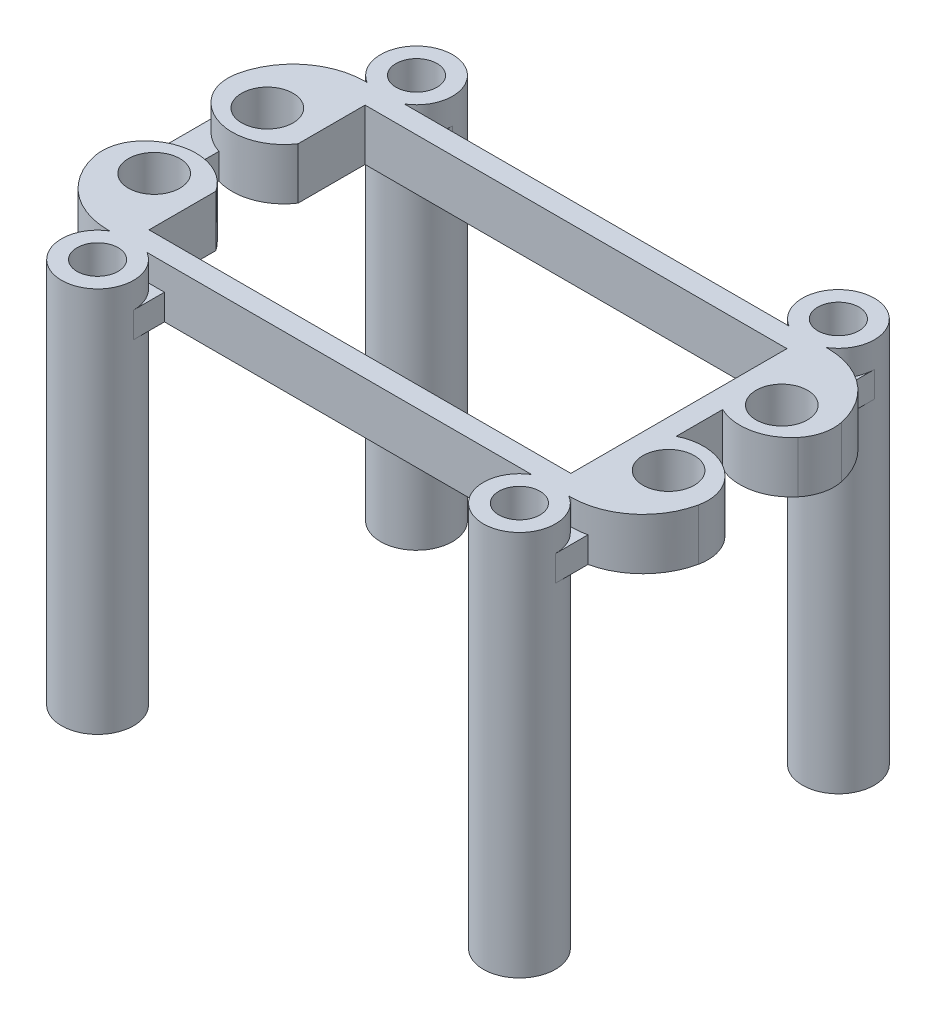
SolidWorks part; units mm, degrees
ref_plane "Front Plane" through (0, 0, 0) normal (0, 0, 1) x (1, 0, 0)
ref_plane "Top Plane" through (0, 0, 0) normal (0, 1, 0) x (1, 0, 0)
ref_plane "Right Plane" through (0, 0, 0) normal (1, 0, 0) x (0, 0, -1)
sketch "Sketch1" plane through (0, 0, 0) normal (0, 1, 0) x (1, 0, 0)
  line L0 (-20, 0) -> (-22, 0) construction
  line L1 (20.5, 10.5) -> (-20.5, 10.5)
  line L2 (20.5, 10.5) -> (20.5, -10.5)
  line L3 (20.5, -10.5) -> (-20.5, -10.5)
  line L4 (-20.5, 10.5) -> (-20.5, 4)
  line L5 (20.5, 10.5) -> (-20.5, -10.5) construction
  line L6 (20.5, -10.5) -> (-20.5, 10.5) construction
  line L7 (22.5, 12.5) -> (-22.5, 12.5)
  line L8 (22.5, 2.2557) -> (22.5, -2.2557)
  line L9 (22.5, -12.5) -> (-22.5, -12.5)
  line L11 (22.5, 12.5) -> (-22.5, -12.5) construction
  line L12 (22.5, -12.5) -> (-22.5, 12.5) construction
  line L16 (-20.5, -4) -> (-20.5, -10.5)
  line L17 (0, 0) -> (-37.8746, 0) construction
  line L18 (0, 0) -> (0, 8.5057) construction
  circle A0 centre (-25, 5.5) radius 2.5
  circle A1 centre (-25, -5.5) radius 2.5
  arc A4 (-22.5, 12.5) -> (-29.3504, 6.9605) centre (-22.5, 5.4945) ccw
  arc A5 (-20.5, 4) -> (-28.5206, 3.5732) centre (-24.6686, 6.761) cw
  arc A6 (-20.5, -4) -> (-28.5206, -3.5732) centre (-24.6686, -6.761) ccw
  arc A7 (-22.5, -12.5) -> (-29.3504, -6.9605) centre (-22.5, -5.4945) cw
  arc A8 (22.5, -12.5) -> (29.3504, -6.9605) centre (22.5, -5.4945) ccw
  circle A9 centre (25, -5.5) radius 2.5
  arc A10 (22.5, -2.2557) -> (28.5206, -3.5732) centre (24.6686, -6.761) cw
  circle A11 centre (25, 5.5) radius 2.5
  arc A12 (22.5, 2.2557) -> (28.5206, 3.5732) centre (24.6686, 6.761) ccw
  arc A13 (22.5, 12.5) -> (29.3504, 6.9605) centre (22.5, 5.4945) cw
  arc A14 (29.3504, -6.9605) -> (28.5206, -3.5732) centre (25.439, -6.1234) ccw
  arc A15 (28.5206, 3.5732) -> (29.3504, 6.9605) centre (25.439, 6.1234) ccw
  arc A16 (-28.5206, -3.5732) -> (-29.3504, -6.9605) centre (-25.439, -6.1234) ccw
  arc A17 (-29.3504, 6.9605) -> (-28.5206, 3.5732) centre (-25.439, 6.1234) ccw
  point P0 (0, 0)
  point P6 (0, 0)
  point P13 (-21, 0)
  point P36 (29.5055, -5.4945)
  point P46 (29.5055, 5.4945)
  point P49 (-29.5055, -5.4945)
  point P52 (-29.5055, 5.4945)
  dimension "D6" = 5
  dimension "D8" = 4.5
  dimension "D9" = 11
  dimension "D10" = 5
  dimension "D5" = 4
  dimension "D2" = 2
  dimension "D3" = 41
  dimension "D4" = 21
extrude "Boss-Extrude1" add sketch "Sketch1" along normal blind 2.5
sketch "Sketch4" plane through (0, 0, 0) normal (0, 1, 0) x (1, 0, 0)
  line L0 (-20.5, -10.5) -> (-20.5, -12.5) construction
  line L1 (-20.5, 10.5) -> (-20.5, 12.5) construction
  line L2 (22.5, 12.5) -> (-22.5, 12.5) construction
  line L3 (-20.5, 12.5) -> (-20.5, 15.5) construction
  line L4 (0, 0) -> (-12.5316, 0) construction
  line L5 (-22.5, -12.5) -> (22.5, -12.5) construction
  line L6 (-20.5, -12.5) -> (-20.5, -15.5) construction
  circle A0 centre (-20.5, 15.5) radius 2
  circle A1 centre (-20.5, 15.5) radius 3.5
  circle A2 centre (20.5, 15.5) radius 2
  circle A3 centre (20.5, 15.5) radius 3.5
  circle A4 centre (-20.5, -15.5) radius 2
  circle A5 centre (-20.5, -15.5) radius 3.5
  circle A6 centre (20.5, -15.5) radius 2
  circle A7 centre (20.5, -15.5) radius 3.5
  dimension "D1" = 1.5
  dimension "D2" = 4
  dimension "D3" = 1.5
  dimension "D4" = 4
  dimension "D8" = 4
  dimension "D9" = 1.5
  dimension "D10" = 1.5
  dimension "D11" = 4
  dimension "D5" = 41
  dimension "D6" = 3
  dimension "D7" = 41
  dimension "D12" = 3
extrude "Boss-Extrude2" add sketch "Sketch4" along normal up to surface (2.5 mm away) and the other way blind 35 up to face at (0.2335, 2.5, 0)
sketch "Sketch5" plane through (0, 0, 0) normal (0, 1, 0) x (1, 0, 0)
  line L1 (-26.2086, 2.0041) -> (-26.2086, -2.0041)
  line L2 (-29.3241, 5.1717) -> (-29.3241, -5.1717)
  line L29 (-17, 15.5) -> (-17, 12.5)
  line L30 (-17, -15.5) -> (-18.5, -15.5)
  line L31 (-24, -15.5) -> (-24, -12.3375)
  line L32 (-24, 12.3375) -> (-24, 15.5)
  line L33 (-24, 15.5) -> (-22.5, 15.5)
  line L34 (-18.5, 15.5) -> (-17, 15.5)
  line L35 (-22.5, -15.5) -> (-24, -15.5)
  line L36 (-18.6972, -12.5) -> (18.6972, -12.5)
  line L37 (-22.5, -12.5) -> (-22.3028, -12.5)
  line L38 (-20.5, -10.5) -> (-20.5, -4)
  line L39 (20.5, -10.5) -> (-20.5, -10.5)
  line L40 (20.5, 10.5) -> (20.5, -10.5)
  line L41 (-20.5, 10.5) -> (20.5, 10.5)
  line L42 (-20.5, 4) -> (-20.5, 10.5)
  line L43 (-22.3028, 12.5) -> (-22.5, 12.5)
  line L44 (18.6972, 12.5) -> (-18.6972, 12.5)
  line L45 (22.5, 12.5) -> (22.3028, 12.5)
  line L46 (22.5, -2.2557) -> (22.5, 2.2557)
  line L47 (22.3028, -12.5) -> (22.5, -12.5)
  line L48 (-17, -12.5) -> (17, -12.5)
  line L50 (-20.5, -10.5) -> (-20.5, -4)
  line L51 (20.5, -10.5) -> (-20.5, -10.5)
  line L52 (20.5, 10.5) -> (20.5, -10.5)
  line L53 (-20.5, 10.5) -> (20.5, 10.5)
  line L54 (-20.5, 4) -> (-20.5, 10.5)
  line L56 (17, 12.5) -> (-17, 12.5)
  line L58 (22.5, -2.2557) -> (22.5, 2.2557)
  line L60 (17, 15.5) -> (18.5, 15.5)
  line L61 (24, 15.5) -> (24, 12.3375)
  line L62 (24, -15.5) -> (22.5, -15.5)
  line L63 (17, -15.5) -> (17, -12.5)
  line L64 (22.5, 15.5) -> (24, 15.5)
  line L65 (18.5, -15.5) -> (17, -15.5)
  line L66 (24, -12.3375) -> (24, -15.5)
  line L67 (-17, -12.5) -> (-17, -15.5)
  line L68 (17, 12.5) -> (17, 15.5)
  arc A32 (-18.6972, 12.5) -> (-22.3028, 12.5) centre (-20.5, 15.5) ccw construction
  arc A33 (-22.3028, -12.5) -> (-18.6972, -12.5) centre (-20.5, -15.5) ccw construction
  arc A34 (-18.5, -15.5) -> (-22.5, -15.5) centre (-20.5, -15.5) ccw
  arc A35 (-22.5, 15.5) -> (-18.5, 15.5) centre (-20.5, 15.5) ccw
  circle A36 centre (-25, 5.5) radius 2.5
  circle A37 centre (-25, -5.5) radius 2.5
  circle A38 centre (25, -5.5) radius 2.5
  circle A39 centre (25, 5.5) radius 2.5
  arc A40 (22.5, -15.5) -> (18.5, -15.5) centre (20.5, -15.5) ccw
  arc A41 (18.5, 15.5) -> (22.5, 15.5) centre (20.5, 15.5) ccw
  arc A42 (22.3028, 12.5) -> (18.6972, 12.5) centre (20.5, 15.5) ccw construction
  arc A43 (18.6972, -12.5) -> (22.3028, -12.5) centre (20.5, -15.5) ccw construction
  arc A48 (22.3028, -12.5) -> (18.6972, -12.5) centre (20.5, -15.5) ccw
  arc A49 (-18.6972, -12.5) -> (-22.3028, -12.5) centre (-20.5, -15.5) ccw
  arc A50 (-29.3504, -6.9605) -> (-22.5, -12.5) centre (-22.5, -5.4945) ccw
  arc A51 (-28.5206, -3.5732) -> (-29.3504, -6.9605) centre (-25.439, -6.1234) ccw
  arc A52 (-20.5, -4) -> (-28.5206, -3.5732) centre (-24.6686, -6.761) ccw
  arc A53 (-28.5206, 3.5732) -> (-20.5, 4) centre (-24.6686, 6.761) ccw
  arc A54 (-29.3504, 6.9605) -> (-28.5206, 3.5732) centre (-25.439, 6.1234) ccw
  arc A55 (-22.5, 12.5) -> (-29.3504, 6.9605) centre (-22.5, 5.4945) ccw
  arc A56 (-22.3028, 12.5) -> (-18.6972, 12.5) centre (-20.5, 15.5) ccw
  arc A57 (18.6972, 12.5) -> (22.3028, 12.5) centre (20.5, 15.5) ccw
  arc A58 (29.3504, 6.9605) -> (22.5, 12.5) centre (22.5, 5.4945) ccw
  arc A59 (28.5206, 3.5732) -> (29.3504, 6.9605) centre (25.439, 6.1234) ccw
  arc A60 (22.5, 2.2557) -> (28.5206, 3.5732) centre (24.6686, 6.761) ccw
  arc A61 (28.5206, -3.5732) -> (22.5, -2.2557) centre (24.6686, -6.761) ccw
  arc A62 (29.3504, -6.9605) -> (28.5206, -3.5732) centre (25.439, -6.1234) ccw
  arc A63 (22.5, -12.5) -> (29.3504, -6.9605) centre (22.5, -5.4945) ccw
  arc A66 (-29.3504, -6.9605) -> (-24, -12.3375) centre (-22.5, -5.4945) ccw
  arc A67 (-29.3241, -5.1717) -> (-29.3504, -6.9605) centre (-25.439, -6.1234) ccw
  arc A68 (-20.5, -4) -> (-26.2086, -2.0041) centre (-24.6686, -6.761) ccw
  arc A69 (-26.2086, 2.0041) -> (-20.5, 4) centre (-24.6686, 6.761) ccw
  arc A70 (-29.3504, 6.9605) -> (-29.3241, 5.1717) centre (-25.439, 6.1234) ccw
  arc A71 (-24, 12.3375) -> (-29.3504, 6.9605) centre (-22.5, 5.4945) ccw
  arc A74 (29.3504, 6.9605) -> (24, 12.3375) centre (22.5, 5.4945) ccw
  arc A75 (28.5206, 3.5732) -> (29.3504, 6.9605) centre (25.439, 6.1234) ccw
  arc A76 (22.5, 2.2557) -> (28.5206, 3.5732) centre (24.6686, 6.761) ccw
  arc A77 (28.5206, -3.5732) -> (22.5, -2.2557) centre (24.6686, -6.761) ccw
  arc A78 (29.3504, -6.9605) -> (28.5206, -3.5732) centre (25.439, -6.1234) ccw
  arc A79 (24, -12.3375) -> (29.3504, -6.9605) centre (22.5, -5.4945) ccw
  dimension "D1" = 0
extrude "Boss-Extrude3" add sketch "Sketch5" against normal blind 2.5
